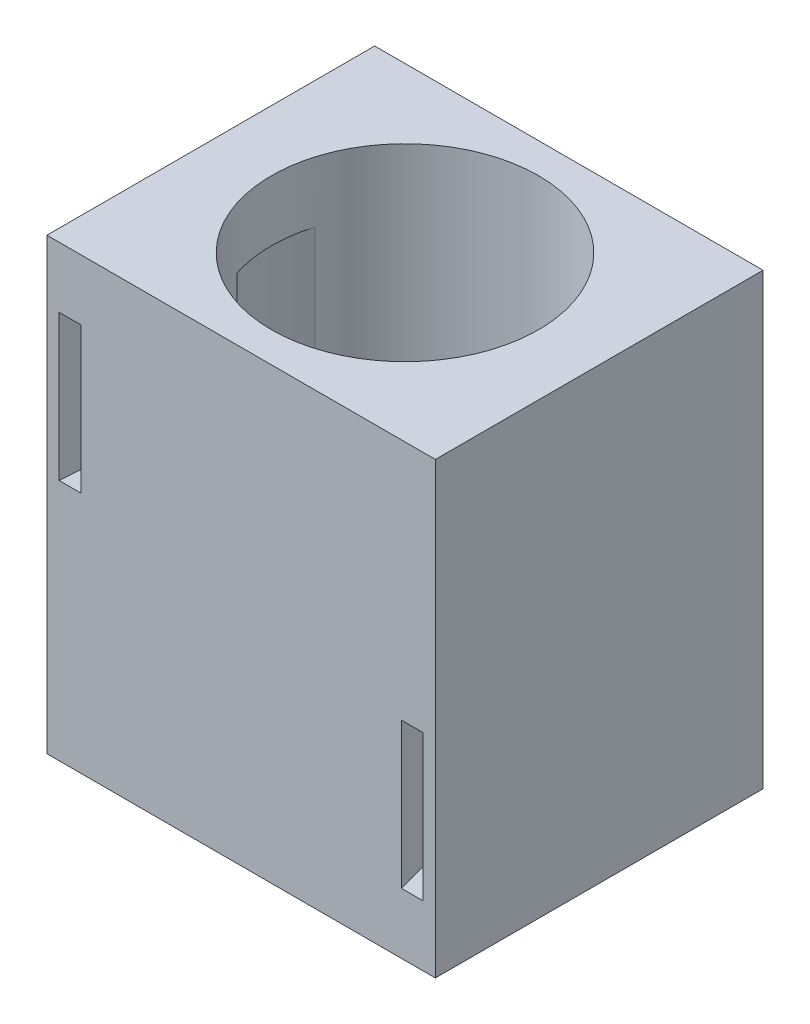
SolidWorks part; units mm, degrees
ref_plane "Front Plane" through (0, 0, 0) normal (0, 0, 1) x (1, 0, 0)
ref_plane "Top Plane" through (0, 0, 0) normal (0, 1, 0) x (1, 0, 0)
ref_plane "Right Plane" through (0, 0, 0) normal (1, 0, 0) x (0, 0, -1)
sketch "Sketch1" plane through (0, 0, 0) normal (0, 1, 0) x (1, 0, 0)
  line L0 (-11, 0) -> (-16, 0) construction
  line L1 (16, 13.5) -> (-16, 13.5)
  line L2 (16, 13.5) -> (16, -13.5)
  line L3 (16, -13.5) -> (-16, -13.5)
  line L4 (-16, 13.5) -> (-16, -13.5)
  line L5 (0, 11) -> (0, 13.5) construction
  line L6 (0, -11) -> (0, -13.5) construction
  line L7 (11, 0) -> (16, 0) construction
  circle A0 centre (0, 0) radius 11
  dimension "D1" = 22
  dimension "D2" = 32
  dimension "D3" = 27
extrude "Boss-Extrude1" add sketch "Sketch1" along normal blind 30
ref_plane "Plane1" through (0, 28.5, 0) normal (0, 1, 0) x (1, 0, 0)
ref_plane "Plane2" through (0, 1.5, 0) normal (0, -1, 0) x (-1, 0, 0)
sketch "Sketch4" plane through (0, 28.5, 0) normal (0, 1, 0) x (1, 0, 0)
  line L0 (0, 0) -> (-16, 0) construction
  line L1 (-16, 13.5) -> (-16, -13.5) construction
  line L2 (-13.2, -13.5) -> (-8.9435, 2.3148)
  line L3 (-16, -13.5) -> (16, -13.5) construction
  line L4 (-10.5411, 3.1441) -> (-8.9435, 2.3148)
  line L5 (-15, -13.5) -> (-13.2, -13.5)
  line L7 (-10.5411, 3.1441) -> (24.9601, -15.2859) construction
  line L8 (24.9601, -15.2859) -> (-15, -13.5) construction
  circle A0 centre (0, 0) radius 11 construction
  arc A2 (-10.5411, 3.1441) -> (-15, -13.5) centre (24.9601, -15.2859) ccw
  circle A3 centre (0, 0) radius 11 construction
  point P14 (-10.5411, 3.1441)
  dimension "D1" = 1
  dimension "D2" = 1.8
  dimension "D3" = 40
extrude "Cut-Extrude2" cut sketch "Sketch4" against normal blind 12
ref_plane "Plane3" through (0, 0, 0) normal (-1, 0, 0) x (0, 0, 1)
ref_plane "Plane4" through (0, 15, 0) normal (0, 1, 0) x (1, 0, 0)
ref_axis "Axis2" through (0, 15, 28.7687) along (0, 0, -1)
pattern_circular "CirPattern2" count 2 every 180 about axis through (0, 15, 28.7687) along (0, 0, -1) of "Cut-Extrude2"
sketch "Sketch7" plane through (0, 30, 0) normal (0, 1, 0) x (1, 0, 0)
  line L4 (-16, 13.5) -> (-16, -13.5)
  line L5 (-16, -13.5) -> (16, -13.5)
  line L6 (16, -13.5) -> (16, 13.5)
  line L7 (16, 13.5) -> (-16, 13.5)
  line L8 (-16, 13.5) -> (-16, -13.5)
  line L9 (-16, -13.5) -> (16, -13.5)
  line L10 (16, -13.5) -> (16, 13.5)
  line L11 (16, 13.5) -> (-16, 13.5)
  circle A0 centre (0, 0) radius 11 construction
  circle A1 centre (0, 0) radius 11
  dimension "D1" = 0
extrude "Boss-Extrude2" add sketch "Sketch7" along normal blind 3.5
sketch "Sketch8" plane through (0, 0, 0) normal (0, -1, 0) x (1, 0, 0)
  line L4 (-16, 13.5) -> (-16, -13.5)
  line L5 (-16, -13.5) -> (16, -13.5)
  line L6 (16, -13.5) -> (16, 13.5)
  line L7 (16, 13.5) -> (-16, 13.5)
  line L8 (-16, 13.5) -> (-16, -13.5)
  line L9 (-16, -13.5) -> (16, -13.5)
  line L10 (16, -13.5) -> (16, 13.5)
  line L11 (16, 13.5) -> (-16, 13.5)
  circle A0 centre (0, 0) radius 11 construction
  circle A1 centre (0, 0) radius 11
  dimension "D1" = 0
extrude "Boss-Extrude3" add sketch "Sketch8" along normal blind 3.5
